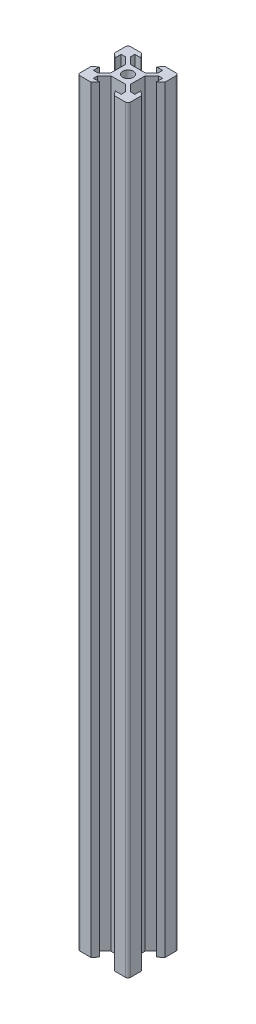
SolidWorks part; units mm, degrees
ref_plane "Front Plane" through (0, 0, 0) normal (0, 0, 1) x (1, 0, 0)
ref_plane "Top Plane" through (0, 0, 0) normal (0, 1, 0) x (1, 0, 0)
ref_plane "Right Plane" through (0, 0, 0) normal (1, 0, 0) x (0, 0, -1)
sketch "Sketch1" plane through (0, 0, 0) normal (0, 1, 0) x (1, 0, 0)
  line L0 (-3.125, 8.2) -> (-4.58, 10)
  line L1 (-9, 10) -> (9, 10)
  line L2 (-10, 9) -> (-10, -9)
  line L3 (-9, -10) -> (9, -10)
  line L4 (10, 9) -> (10, -9)
  line L5 (-10, 10) -> (10, -10) construction
  line L6 (-10, -10) -> (10, 10) construction
  line L7 (-10, 0) -> (0, 0) construction
  line L8 (0, 10) -> (0, 0) construction
  line L9 (-8.2, 3.125) -> (-10, 4.58)
  line L10 (-8.2, 3.125) -> (-8.2, 5.5)
  line L11 (-3.125, 8.2) -> (-5.5, 8.2)
  line L12 (-5.5, 8.2) -> (-5.5, 6.56)
  line L13 (-2.84, 3.9) -> (2.84, 3.9)
  line L14 (-5.5, 6.56) -> (-2.84, 3.9)
  line L15 (-8.2, 5.5) -> (-6.56, 5.5)
  line L16 (-6.56, 5.5) -> (-3.9, 2.84)
  line L17 (-3.9, 2.84) -> (-3.9, -2.84)
  line L18 (3.9, 2.84) -> (3.9, -2.84)
  line L19 (6.56, 5.5) -> (3.9, 2.84)
  line L20 (8.2, 5.5) -> (6.56, 5.5)
  line L21 (8.2, 3.125) -> (8.2, 5.5)
  line L22 (8.2, 3.125) -> (10, 4.58)
  line L23 (3.125, 8.2) -> (4.58, 10)
  line L24 (3.125, 8.2) -> (5.5, 8.2)
  line L25 (5.5, 8.2) -> (5.5, 6.56)
  line L26 (5.5, 6.56) -> (2.84, 3.9)
  line L27 (-8.2, -3.125) -> (-10, -4.58)
  line L28 (-8.2, -3.125) -> (-8.2, -5.5)
  line L29 (-8.2, -5.5) -> (-6.56, -5.5)
  line L30 (-6.56, -5.5) -> (-3.9, -2.84)
  line L31 (8.2, -3.125) -> (10, -4.58)
  line L32 (8.2, -3.125) -> (8.2, -5.5)
  line L33 (8.2, -5.5) -> (6.56, -5.5)
  line L34 (6.56, -5.5) -> (3.9, -2.84)
  line L35 (5.5, -6.56) -> (2.84, -3.9)
  line L36 (5.5, -8.2) -> (5.5, -6.56)
  line L37 (3.125, -8.2) -> (5.5, -8.2)
  line L38 (3.125, -8.2) -> (4.58, -10)
  line L39 (-5.5, -6.56) -> (-2.84, -3.9)
  line L40 (-2.84, -3.9) -> (2.84, -3.9)
  line L41 (-5.5, -8.2) -> (-5.5, -6.56)
  line L42 (-3.125, -8.2) -> (-5.5, -8.2)
  line L43 (-3.125, -8.2) -> (-4.58, -10)
  circle A0 centre (0, 0) radius 2.1
  arc A1 (-10, -9) -> (-9, -10) centre (-9, -9) ccw
  arc A2 (9, -10) -> (10, -9) centre (9, -9) ccw
  arc A3 (9, 10) -> (10, 9) centre (9, 9) cw
  arc A4 (-9, 10) -> (-10, 9) centre (-9, 9) ccw
  point P0 (0, 0)
  point P35 (0, 3.9)
  point P40 (-3.9, 0)
  point P41 (3.9, 0)
  dimension "D3" = 4.2
  dimension "D2" = 1
  dimension "D1" = 20
  dimension "D4" = 6.1
  dimension "D5" = 6.25
  dimension "D6" = 11
  dimension "D7" = 5.68
  dimension "D8" = 9.16
  dimension "D9" = 1.8
extrude "Boss-Extrude1" add sketch "Sketch1" along normal blind 300 contours L43 L42 L41 L39 L40 L35 L36 L37 L38 L3 L4 L31 L32 L33 L34 L18 L19 L20 L21 L22 L1 L23 L24 L25 L26 L13 L14 L12 L11 L0 L2 L9 L10 L15 L16 L17 L30 L29 L28 L27 A0 region at (-4.3125, 0, -8.4828)
